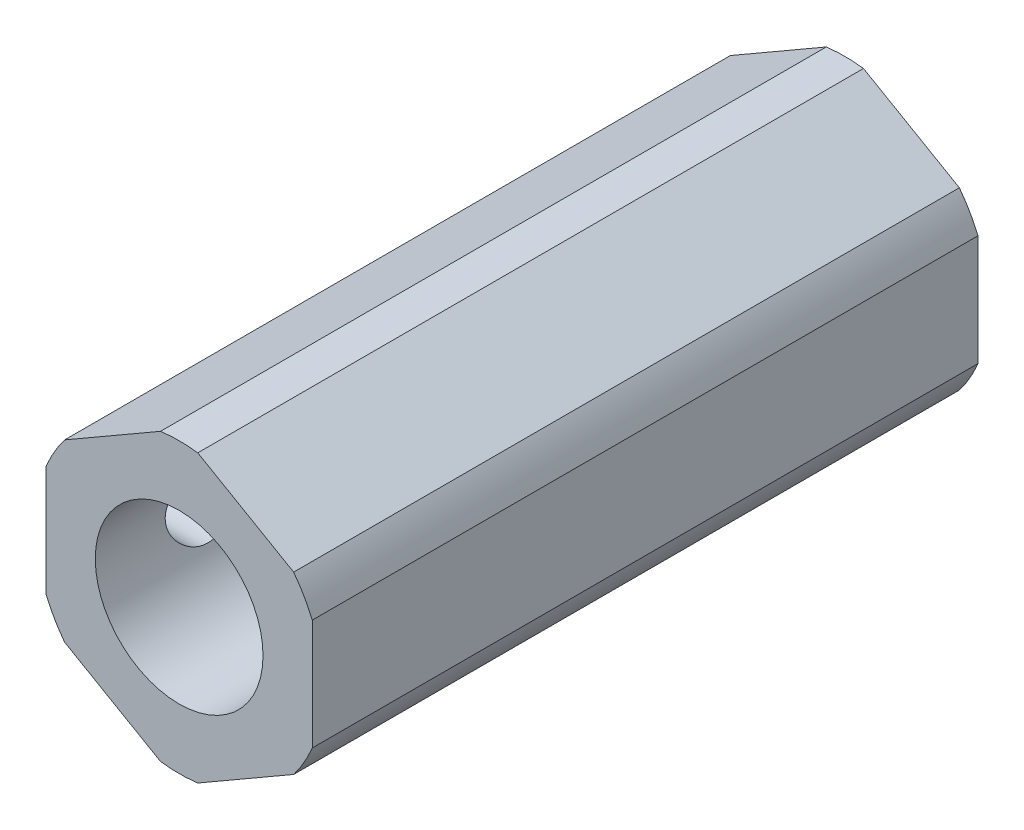
SolidWorks part; units mm, degrees
material "ThunderHex"
ref_plane "Front Plane" through (0, 0, 0) normal (0, 0, 1) x (1, 0, 0)
ref_plane "Top Plane" through (0, 0, 0) normal (0, 1, 0) x (1, 0, 0)
ref_plane "Right Plane" through (0, 0, 0) normal (1, 0, 0) x (0, 0, -1)
ref_plane "End1" through (0, 0, 15.875) normal (0, 0, 1) x (1, 0, 0)
ref_plane "End2" through (0, 0, -15.875) normal (0, 0, 1) x (1, 0, 0)
sketch "Sketch1" plane through (0, 0, 0) normal (0, 0, 1) x (1, 0, 0)
  circle A0 centre (0, 0) radius 6.35
  dimension "D1" = 12.7
extrude "Basic Rod" add sketch "Sketch1" along normal up to surface (15.875 mm away) and the other way up to surface (15.875 mm away) up to plane "End1" other way up to plane "End2"
ref_axis "Center Axis" through (0, 0, -19.2087) along (0, 0, 1)
sketch "Sketch8" plane through (0, 0, 0) normal (0, 0, 1) x (1, 0, 0)
  line L0 (-5.4616, 4.1791) -> (-6.35, 3.6662) construction
  line L1 (-0.8884, 6.8194) -> (-5.4616, 4.1791)
  line L2 (-6.35, 2.6403) -> (-6.35, -2.6403)
  line L3 (-5.4616, -4.1791) -> (-0.8884, -6.8194)
  line L4 (0.8884, -6.8194) -> (5.4616, -4.1791)
  line L5 (6.35, -2.6403) -> (6.35, 2.6403)
  line L6 (5.4616, 4.1791) -> (0.8884, 6.8194)
  line L7 (-6.35, 3.6662) -> (-6.35, 2.6403) construction
  line L8 (0, 7.3323) -> (-0.8884, 6.8194) construction
  line L9 (0.8884, 6.8194) -> (0, 7.3323) construction
  line L10 (6.35, 3.6662) -> (5.4616, 4.1791) construction
  line L11 (6.35, 2.6403) -> (6.35, 3.6662) construction
  line L12 (6.35, -3.6662) -> (6.35, -2.6403) construction
  line L13 (5.4616, -4.1791) -> (6.35, -3.6662) construction
  line L14 (0, -7.3323) -> (0.8884, -6.8194) construction
  line L15 (-0.8884, -6.8194) -> (0, -7.3323) construction
  line L16 (-6.35, -3.6662) -> (-5.4616, -4.1791) construction
  line L17 (-6.35, -2.6403) -> (-6.35, -3.6662) construction
  circle A0 centre (0, 0) radius 6.35 construction
  arc A1 (-6.35, -2.6403) -> (-5.4616, -4.1791) centre (0, 0) ccw
  circle A2 centre (0, 0) radius 6.35 construction
  arc A3 (-6.35, 2.6403) -> (-6.35, -2.6403) centre (0, 0) ccw construction
  arc A4 (-0.8884, 6.8194) -> (-5.4616, 4.1791) centre (0, 0) ccw construction
  arc A5 (-5.4616, 4.1791) -> (-6.35, 2.6403) centre (0, 0) ccw
  arc A6 (5.4616, 4.1791) -> (0.8884, 6.8194) centre (0, 0) ccw construction
  arc A7 (0.8884, 6.8194) -> (-0.8884, 6.8194) centre (0, 0) ccw
  arc A8 (6.35, -2.6403) -> (6.35, 2.6403) centre (0, 0) ccw construction
  arc A9 (6.35, 2.6403) -> (5.4616, 4.1791) centre (0, 0) ccw
  arc A10 (0.8884, -6.8194) -> (5.4616, -4.1791) centre (0, 0) ccw construction
  arc A11 (5.4616, -4.1791) -> (6.35, -2.6403) centre (0, 0) ccw
  arc A12 (-5.4616, -4.1791) -> (-0.8884, -6.8194) centre (0, 0) ccw construction
  arc A13 (-0.8884, -6.8194) -> (0.8884, -6.8194) centre (0, 0) ccw
  dimension "D1" = 13.7541
extrude "THex" add sketch "Sketch8" along normal mid plane 31.75
sketch "Sketch5" plane through (0, 0, 0) normal (0, 0, 1) x (1, 0, 0)
  line L1 (-3.6662, 6.35) -> (-7.3323, 0)
  line L2 (-7.3323, 0) -> (-3.6662, -6.35)
  line L3 (-3.6662, -6.35) -> (3.6662, -6.35)
  line L4 (3.6662, -6.35) -> (7.3323, 0)
  line L5 (7.3323, 0) -> (3.6662, 6.35)
  line L6 (3.6662, 6.35) -> (-3.6662, 6.35)
  circle A0 centre (0, 0) radius 6.35 construction
  circle A2 centre (0, 0) radius 6.35 construction
extrude "Hex" [suppressed] add sketch "Sketch5" along normal mid plane 31.75
sketch "Sketch7" plane through (0, 0, 0) normal (1, 0, 0) x (0, 0, -1)
  line L0 (0, 0) -> (-50000, 0) construction
  line L1 (-15.875, 5.9436) -> (-16.891, 5.9436)
  line L2 (-16.891, 5.9436) -> (-16.891, 6.35)
  line L3 (-16.891, 6.35) -> (-17.907, 6.35)
  line L4 (-18.415, 5.842) -> (-18.415, 0)
  line L5 (-18.415, 0) -> (-15.875, 0)
  line L6 (-15.875, 0) -> (-15.875, 5.9436)
  line L7 (-17.907, 6.35) -> (-18.415, 5.842)
  line L8 (19.2087, 0) -> (-19.2087, 0) construction
  line L9 (-15.875, 5.2388) -> (-15.875, -5.2388) construction
  point P7 (-18.415, 6.35)
  dimension "D1" = 12.7
  dimension "D4" = 1.016
  dimension "D2" = 0.4064
  dimension "D3" = 2.54
revolve "1stSnapRing" [suppressed] add sketch "Sketch7" angle 360 about axis through (0, 0, -19.2087) along (0, 0, 1)
mirror "2ndSnapRing" [suppressed] about plane through (0, 0, 0) normal (0, 0, 1)
sketch "Sketch2" plane through (0, 0, 0) normal (0, 0, 1) x (1, 0, 0)
  circle A0 centre (0, 0) radius 2.1158
  dimension "D1" = 4.2316
extrude "Internal Cut" cut sketch "Sketch2" against normal through all both and the other way through all
sketch "Sketch9" plane through (0, 0, 15.875) normal (0, 0, 1) x (1, 0, 0)
  circle A0 centre (0, 0) radius 4
  dimension "D1" = 8
extrude "Cut-Extrude1" cut sketch "Sketch9" against normal blind 20
sketch "Sketch10" plane through (-6.35, 0, 0) normal (-1, 0, 0) x (0, 0, 1)
  line L0 (15.875, 0) -> (10.8737, 0) construction
  line L1 (15.875, 2.6403) -> (15.875, -2.6403) construction
  line L2 (10.8737, 0) -> (2.8727, 0) construction
  circle A0 centre (2.8727, 0) radius 1.6662
  circle A1 centre (10.8737, 0) radius 1.6662
  dimension "D1" = 3.3325
  dimension "D2" = 5.0013
  dimension "D3" = 8.001
extrude "Cut-Extrude2" cut sketch "Sketch10" against normal up to next
equation "\"Unit Measure\"= \"Length\"'in"
equation "\"D1@Sketch1\"=\"OD\""
equation "\"D1\"= \"Length\""
equation "\"D1@Sketch2\"=\"ID\""
equation "\"Internal Cut\"= IIF ( \"ID\" = 0 ,  suppressed  ,  unsuppressed  ) "
equation "\"D1@Hex\" = \"Length\""
equation "\"Hex\" = IIF ( \"SelectionType\" = 1 , \"suppressed\" , iif ( \"SelectionType\" = 2 , \"suppressed\" , \"unsuppressed\" ) )"
equation "\"OutsideDiameter\"= \"OD\"'in"
equation "\"ThunderHexDia\"= iif ( \"OD\" < .36 , \"OD\" * 1.1 , iif ( \"OD\" < .40 , .4035 , iif ( \"OD\" < .52 , .5415 , \"OD\" * 1.1 ) ) )"
equation "\"D1@Sketch7\"=\"Thickness\""
equation "\"SRDia\"= iif ( \"OD\" = .5 , ( \"OD\" - .468 ) / 2 , iif ( \"OD\" = .375 , ( \"OD\" - .352 ) / 2 , .050 ) )"
equation "\"D2@Sketch7\"= \"SnapRingDepth\""
equation "\"1stSnapRing\"= iif ( \"SnapRingCount\" > 0 , \"unsuppressed\" , \"suppressed\" )"
equation "\"2ndSnapRing\"= iif ( \"SnapRingCount\" = 2 , \"unsuppressed\" , \"suppressed\" )"
equation "\"D1@End1\" = \"Length\" / 2"
equation "\"D1@End2\" = \"Length\""
equation "\"D1@Sketch8\"=\"ThunderHexDia\""
equation "\"D1@THex\" = \"Length\""
equation "\"THex\"= IIF ( \"SelectionType\" = 0 ,  suppressed  , iif ( \"SelectionType\" = 2 ,  suppressed  ,  unsuppressed  )  ) "
